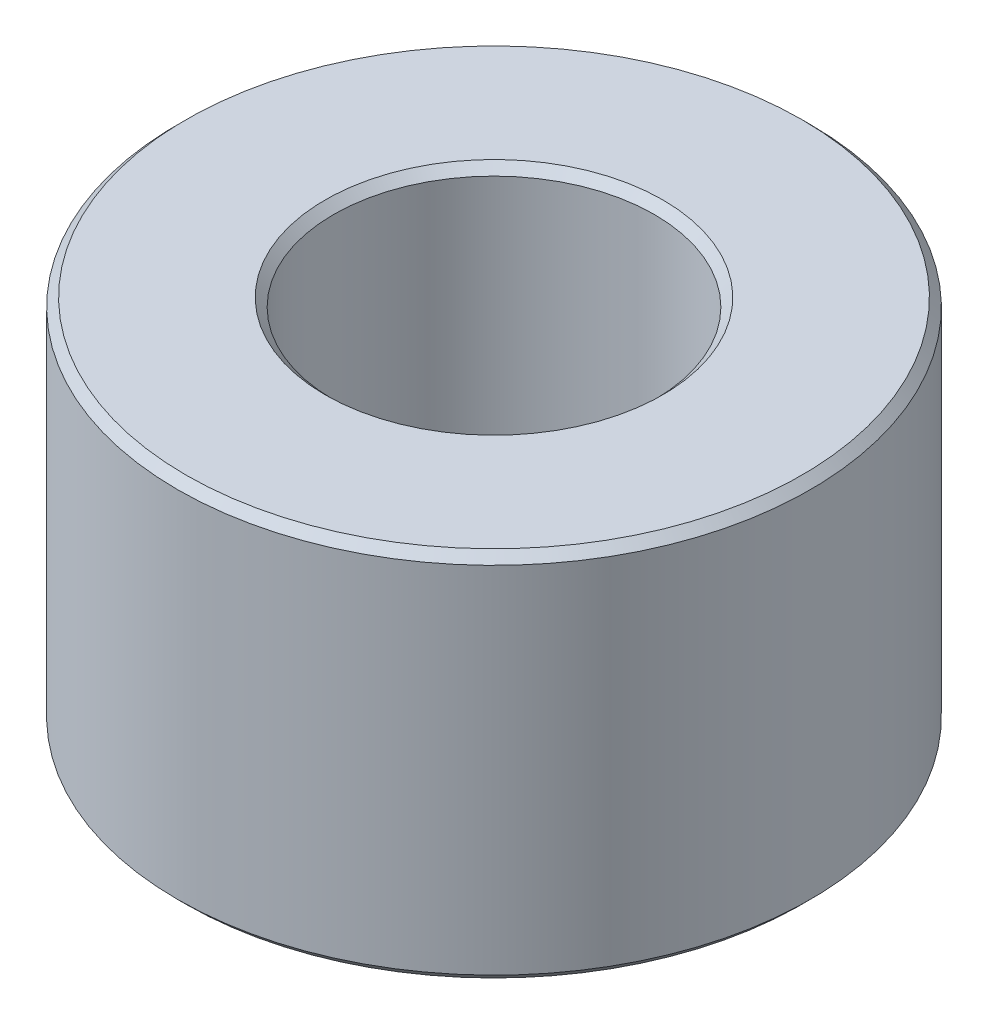
SolidWorks part; units mm, degrees
ref_plane "Front Plane" through (0, 0, 0) normal (0, 0, 1) x (1, 0, 0)
ref_plane "Top Plane" through (0, 0, 0) normal (0, 1, 0) x (1, 0, 0)
ref_plane "Right Plane" through (0, 0, 0) normal (1, 0, 0) x (0, 0, -1)
sketch "Sketch1" plane through (0, 0, 0) normal (0, 1, 0) x (1, 0, 0)
  circle A0 centre (0, 0) radius 32.5
  dimension "SLEEVE_OD" = 65
extrude "Boss-Extrude1" add sketch "Sketch1" along normal blind 38.1927
sketch "Sketch2" plane through (0, 0, 0) normal (0, 1, 0) x (1, 0, 0)
  circle A0 centre (0, 0) radius 16.4836
  dimension "BORE_D" = 32.9671
extrude "Cut-Extrude1" cut sketch "Sketch2" along normal through all
chamfer "Chamfer1" distance 0.8655 angle 45 4 edges at (0, 38.1927, 16.4836) (0, 0, 16.4836) (0, 0, 32.5) (0, 38.1927, 32.5)
